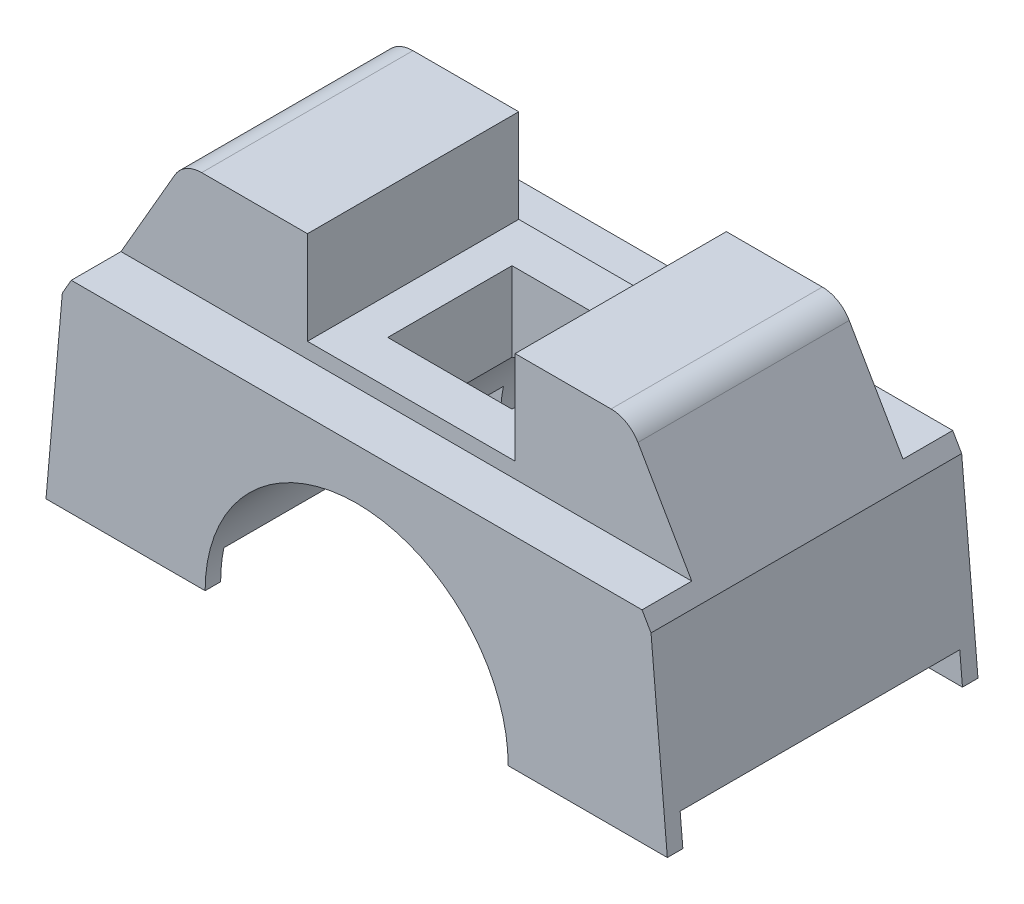
SolidWorks part; units mm, degrees
ref_plane "Front Plane" through (0, 0, 0) normal (0, 0, 1) x (1, 0, 0)
ref_plane "Top Plane" through (0, 0, 0) normal (0, 1, 0) x (1, 0, 0)
ref_plane "Right Plane" through (0, 0, 0) normal (1, 0, 0) x (0, 0, -1)
sketch "Sketch1" plane through (0, 0, 0) normal (0, 0, 1) x (1, 0, 0)
  line L11 (-24.39, 0) -> (-50, 0)
  line L15 (50, 0) -> (24.39, 0)
  line L16 (-15.9172, 50) -> (-15.9172, 35)
  line L17 (-15.9172, 35) -> (17.5, 35)
  line L18 (17.5, 35) -> (17.5, 50)
  line L19 (-50, 0) -> (-47.3753, 30)
  line L20 (-47.3753, 30) -> (-37.2717, 47.5)
  line L21 (50, 0) -> (47.3753, 30)
  line L22 (47.3753, 30) -> (37.2717, 47.5)
  line L23 (-45.932, 32.5) -> (45.932, 32.5)
  line L24 (-32.9416, 50) -> (-15.9172, 50)
  line L25 (17.5, 50) -> (32.9416, 50)
  arc A0 (24.39, 0) -> (-24.39, 0) centre (0, 0) ccw
  arc A1 (37.2717, 47.5) -> (32.9416, 50) centre (32.9416, 45) ccw
  arc A2 (-37.2717, 47.5) -> (-32.9416, 50) centre (-32.9416, 45) cw
  point P15 (35.8283, 50)
  point P18 (-35.8283, 50)
  dimension "D3" = 48.78
  dimension "D4" = 5
  dimension "D2" = 100
  dimension "D5" = 5
  dimension "D6" = 15
  dimension "D7" = 95
  dimension "D8" = 95
  dimension "D9" = 25
  dimension "D10" = 25
  dimension "D11" = 20
  dimension "D12" = 20
  dimension "D13" = 2.5
extrude "Boss-Extrude2" add sketch "Sketch1" along normal mid plane 50
extrude "Boss-Extrude3" add sketch "Sketch1<7>" along normal mid plane 34 contours A2 L20 L22 A1 L25 L18 L17 L16 L24 region at (-40.792, 39.5324, 0)
sketch "Sketch1<7>" plane through (0, 0, 0) normal (0, 0, 1) x (1, 0, 0) same geometry as "Sketch1"
sketch "Sketch3" plane through (0, 35, 0) normal (0, 1, 0) x (1, 0, 0)
  line L1 (-10, 10) -> (10, 10)
  line L2 (10, 10) -> (10, -10)
  line L3 (10, -10) -> (-10, -10)
  line L7 (-10, 10) -> (-10, -10)
  dimension "D4" = 20
extrude "Cut-Extrude1" cut sketch "Sketch3" against normal through all both and the other way through all
sketch "Sketch5" plane through (0, 0, 0) normal (1, 0, 0) x (0, 0, -1)
  line L0 (-22.5, 0) -> (-22.5, 5)
  line L1 (-25, 0) -> (25, 0) construction
  line L2 (-22.5, 5) -> (22.5, 5)
  line L3 (22.5, 5) -> (22.5, 0)
  line L4 (22.5, 0) -> (25, 0)
  line L5 (-22.5, 0) -> (-25, 0)
  dimension "D1" = 2.5
  dimension "D2" = 2.5
  dimension "D3" = 5
extrude "Cut-Extrude2" cut sketch "Sketch5" against normal through all both and the other way through all
